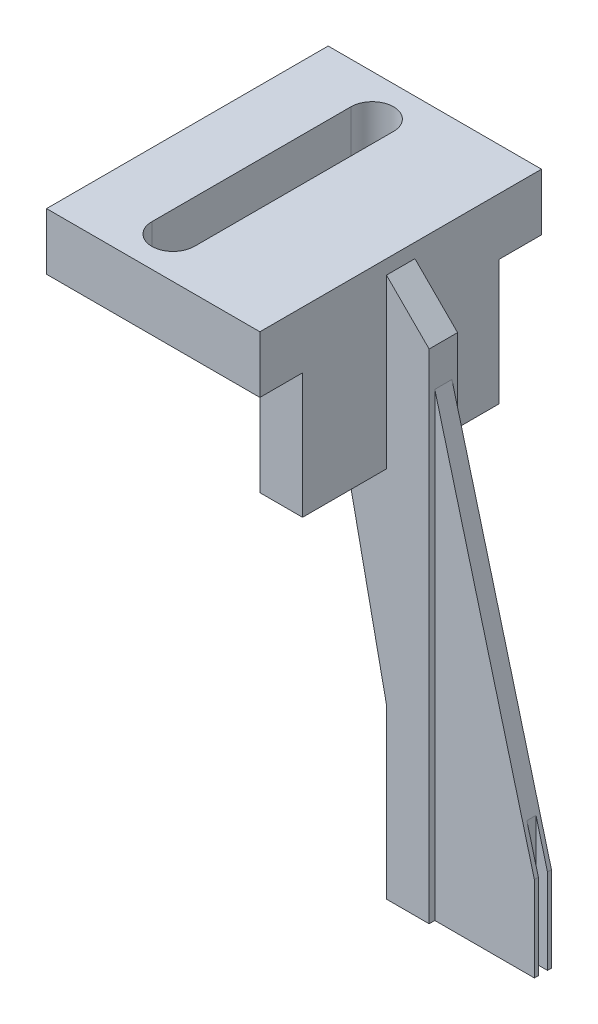
SolidWorks part; units mm, degrees
ref_plane "Front Plane" through (0, 0, 0) normal (0, 0, 1) x (1, 0, 0)
ref_plane "Top Plane" through (0, 0, 0) normal (0, 1, 0) x (1, 0, 0)
ref_plane "Right Plane" through (0, 0, 0) normal (1, 0, 0) x (0, 0, -1)
sketch "Sketch1" plane through (0, 0, 0) normal (1, 0, 0) x (0, 0, -1)
  line L1 (-6.9, -4.4) -> (6.9, -4.4)
  line L2 (-6.9, -4.4) -> (-6.9, 4.4)
  line L3 (-6.9, 4.4) -> (6.9, 4.4)
  line L4 (6.9, -4.4) -> (6.9, 4.4)
  line L5 (-6.9, -4.4) -> (6.9, 4.4) construction
  line L6 (-6.9, 4.4) -> (6.9, -4.4) construction
  point P0 (0, 0)
  dimension "D1" = 13.8
  dimension "D2" = 8.8
extrude "Boss-Extrude1" add sketch "Sketch1" along normal blind 3
sketch "Sketch2" plane through (3, 0, 0) normal (1, 0, 0) x (0, 0, -1)
  line L0 (6.9, 4.4) -> (-6.9, 4.4) construction
  line L1 (1, 4.4) -> (-1, 4.4)
  line L2 (1, 4.4) -> (1, -30.6)
  line L3 (1, -30.6) -> (-1, -30.6)
  line L4 (-1, 4.4) -> (-1, -30.6)
  line L5 (-6.9, -4.4) -> (6.9, -4.4) construction
  line L6 (-6.9, -4.4) -> (6.9, -4.4) construction
  point P8 (0, -4.4)
  point P9 (0, -30.6)
  dimension "D1" = 2
  dimension "D2" = 26.2
extrude "Boss-Extrude2" add sketch "Sketch2" along normal blind 3
sketch "Sketch3" plane through (6, 0, 0) normal (1, 0, 0) x (0, 0, -1)
  line L1 (-0.6, -30.6) -> (0.6, -30.6)
  line L2 (-0.6, -30.6) -> (-0.6, -24.6)
  line L3 (-0.6, -24.6) -> (0.6, -24.6)
  line L4 (0.6, -30.6) -> (0.6, -24.6)
  line L5 (-1, -30.6) -> (1, -30.6) construction
  point P10 (0, -30.6)
  point P11 (0, -30.6)
  dimension "D1" = 1.2
  dimension "D2" = 6
extrude "Boss-Extrude3" add sketch "Sketch3" along normal blind 7
fillet "Fillet3" radius 10 1 edges at (3, -4.4, 0)
sketch "Sketch5" plane through (0, 4.4, 0) normal (0, 1, 0) x (1, 0, 0)
  line L0 (3, 6.9) -> (0, 6.9) construction
  line L1 (3, -6.9) -> (-12, -6.9)
  line L2 (3, -6.9) -> (3, 6.9)
  line L3 (3, 6.9) -> (-12, 6.9)
  line L4 (-12, -6.9) -> (-12, 6.9)
  dimension "D1" = 15
extrude "Boss-Extrude4" add sketch "Sketch5" along normal blind 4
sketch "Sketch6" plane through (0, 4.4, 0) normal (0, -1, 0) x (1, 0, 0)
  line L0 (-6, 3) -> (-6, -3) construction
  line L1 (0, -6.9) -> (0, 6.9) construction
  circle A0 centre (-6, 3) radius 1.5
  circle A1 centre (-6, -3) radius 1.5
  point P4 (0, 0)
  point P7 (-6, 0)
  dimension "D1" = 3
  dimension "D2" = 6
  dimension "D3" = 6
extrude "Cut-Extrude4" cut sketch "Sketch6" against normal through all
sketch "Sketch8" plane through (0, 0, -1) normal (0, 0, -1) x (-1, 0, 0)
  line L0 (-3, -18.7582) -> (0, -4.4)
  line L1 (-3, -30.6) -> (-3, -11.5414) construction
  line L2 (0, -4.4) -> (-3, -4.4)
  line L3 (-3, -4.4) -> (-3, -18.7582)
extrude "Boss-Extrude5" add sketch "Sketch8" against normal up to surface (2 mm away) up to face at (3.5314, -10.3485, 1)
chamfer "Chamfer2" distance 3 angle 45 1 edges at (3, 4.4, 0)
sketch "Sketch11" plane through (0, 0, -0.6) normal (0, 0, -1) x (-1, 0, 0)
  line L0 (-6, -24.6) -> (-13, -24.6)
  line L1 (-13, -24.6) -> (-6, 1.7425)
  line L2 (-6, 1.7425) -> (-6, -24.6)
  point P4 (-6, 1.7425)
extrude "Boss-Extrude7" add sketch "Sketch11" against normal up to surface (1.2 mm away) up to face at (9.5, -27.6, 0.6)
sketch "Sketch12" plane through (0, 0, -6.9) normal (0, 0, -1) x (-1, 0, 0)
  line L0 (-3, -4.4) -> (-3, 8.4) construction
  line L1 (12, 8.4) -> (-3, 8.4)
  line L2 (12, 8.4) -> (12, 4.4)
  line L3 (12, 4.4) -> (-3, 4.4)
  line L4 (-3, 8.4) -> (-3, 4.4)
  line L5 (0, 4.4) -> (12, 4.4) construction
extrude "Boss-Extrude8" add sketch "Sketch12" along normal blind 3
sketch "Sketch13" plane through (0, 0, 6.9) normal (0, 0, 1) x (1, 0, 0)
  line L0 (3, 8.4) -> (3, -4.4) construction
  line L1 (-12, 8.4) -> (3, 8.4)
  line L2 (-12, 8.4) -> (-12, 4.4)
  line L3 (-12, 4.4) -> (3, 4.4)
  line L4 (3, 8.4) -> (3, 4.4)
  line L5 (-12, 4.4) -> (0, 4.4) construction
extrude "Boss-Extrude9" add sketch "Sketch13" along normal blind 3
sketch "Sketch14" plane through (0, 8.4, 0) normal (0, 1, 0) x (1, 0, 0)
  line L0 (-6, 3) -> (-6, -3) construction
  line L2 (-7.5, 7) -> (-7.5, -7)
  line L4 (-4.5, 7) -> (-4.5, -7)
  arc A0 (-7.5, 7) -> (-4.5, 7) centre (-6, 7) cw
  arc A1 (-4.5, -7) -> (-7.5, -7) centre (-6, -7) cw
  point P8 (-6, 0)
  point P10 (-4.5, 0)
  dimension "D1" = 3
  dimension "D2" = 14
extrude "Cut-Extrude7" cut sketch "Sketch14" against normal through all both and the other way through all
sketch "Sketch15" plane through (0, -30.6, 0) normal (0, -1, 0) x (1, 0, 0)
  line L0 (13, 0.6) -> (13, -0.6) construction
  line L1 (13, 0.32) -> (12.1921, 0.32)
  line L2 (13, 0.32) -> (13, -0.32)
  line L3 (13, -0.32) -> (12.1921, -0.32)
  line L4 (12.1921, 0.32) -> (12.1921, -0.32)
  line L5 (11.9922, 0.6) -> (11.9922, -0.6) construction
  line L6 (13, 0.6) -> (6, 0.6) construction
  line L7 (13, -0.6) -> (6, -0.6) construction
  point P13 (13, 0)
  point P14 (11.9922, 0)
  dimension "D1" = 0.28
extrude "Cut-Extrude8" cut sketch "Sketch15" against normal through all both and the other way through all
sketch "Sketch16" plane through (12.1921, 0, 0) normal (1, 0, 0) x (0, 0, -1)
  line L0 (0.32, -21.5597) -> (0.32, -30.6) construction
  line L1 (-0.32, -30.6) -> (0.32, -30.6)
  line L2 (-0.32, -30.6) -> (-0.32, -30)
  line L3 (-0.32, -30) -> (0.32, -30)
  line L4 (0.32, -30.6) -> (0.32, -30)
  dimension "D1" = 0.6
extrude "Cut-Extrude9" cut sketch "Sketch16" against normal through all both and the other way through all
chamfer "Chamfer3" distance 1 angle 45 1 edges at (12.1921, -30, 0)
